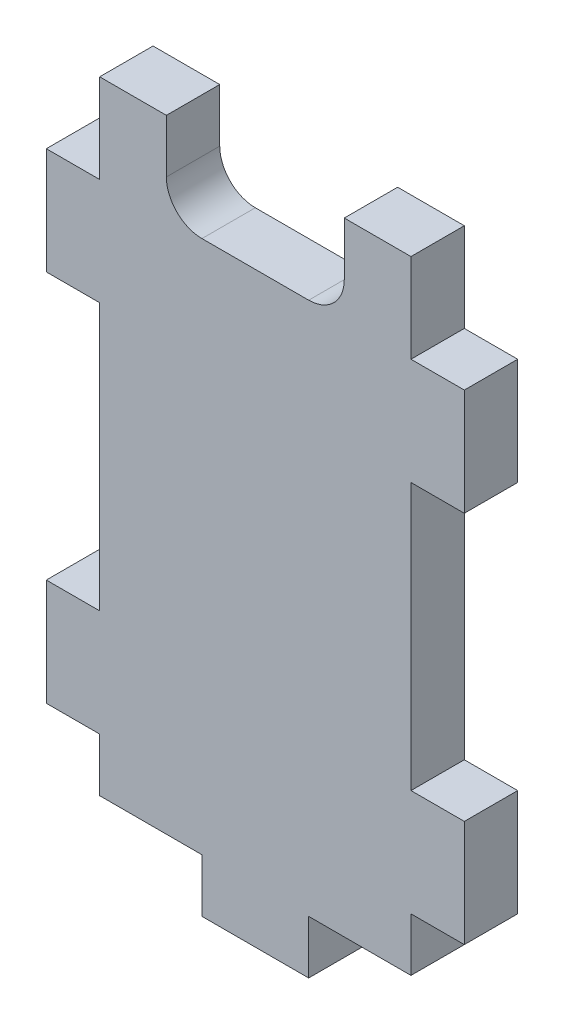
SolidWorks part; units mm, degrees
ref_plane "Front Plane" through (0, 0, 0) normal (0, 0, 1) x (1, 0, 0)
ref_plane "Top Plane" through (0, 0, 0) normal (0, 1, 0) x (1, 0, 0)
ref_plane "Right Plane" through (0, 0, 0) normal (1, 0, 0) x (0, 0, -1)
sketch "Sketch2" plane through (0, 0, 0) normal (0, 1, 0) x (1, 0, 0)
  line L0 (0, 0) -> (0, 6) construction
  dimension "D1" = 6
sketch "Sketch1" plane through (0, 0, 0) normal (0, 0, 1) x (1, 0, 0)
  line L0 (0, -35) -> (0, -41)
  line L1 (-17.5, -35) -> (17.5, -35)
  line L2 (-17.5, -35) -> (-17.5, 35)
  line L3 (-17.5, 35) -> (17.5, 35)
  line L4 (17.5, -35) -> (17.5, 35)
  line L5 (-17.5, -35) -> (17.5, 35)
  line L6 (-17.5, 35) -> (17.5, -35)
  line L7 (0, -41) -> (-6, -41)
  line L8 (-6, -41) -> (-6, -35)
  line L9 (-6, -35) -> (6, -35)
  line L10 (6, -35) -> (6, -41)
  line L11 (6, -41) -> (0, -41)
  line L12 (23.5, -29) -> (23.5, -35) construction
  line L13 (17.5, 25) -> (23.5, 25)
  line L14 (17.5, 25) -> (17.5, 13)
  line L15 (17.5, 13) -> (23.5, 13)
  line L16 (23.5, 25) -> (23.5, 13)
  line L17 (17.5, -17) -> (23.5, -17)
  line L18 (17.5, -17) -> (17.5, -29)
  line L19 (17.5, -29) -> (23.5, -29)
  line L20 (23.5, -17) -> (23.5, -29)
  line L22 (23.5, -35) -> (17.5, -35) construction
  line L23 (10, 35) -> (10, 25)
  line L24 (10, 25) -> (-10, 25)
  line L25 (-10, 25) -> (-10, 35)
  line L26 (0, 25) -> (0, 35) construction
  line L27 (17.5, 25) -> (10, 25) construction
  point P0 (0, 0)
  dimension "D1" = 70
  dimension "D2" = 35
  dimension "D3" = 6
  dimension "D4" = 12
  dimension "D5" = 12
  dimension "D6" = 10
  dimension "D7" = 20
extrude "Boss-Extrude1" add sketch "Sketch1" against normal up to vertex (6 mm away) contours L6 L2 L5 | L24 L25 L3 L6 L5 L23 | L5 L6 L4 | L6 L5 L1 | L11 L10 L1 L0 | L8 L7 L0 L1 region at (3, -38, 0) region at (-3, -38, 0) region at (0, -23.3333, 0) region at (-11.6667, 0, 0) region at (11.6667, 0, 0) region at (0, 20.101, 0) up to point (0, 0, -6)
extrude "Boss-Extrude2" add sketch "Sketch1<3>" against normal up to surface (6 mm away) contours L16 L13 L4 L15 | L20 L17 L4 L19 region at (20.5, -23, 0) region at (20.5, 19, 0) up to face at (0, -2.6667, -6)
sketch "Sketch1<3>" plane through (0, 0, 0) normal (0, 0, 1) x (1, 0, 0) same geometry as "Sketch1"
mirror "Mirror1" about plane through (0, 0, 0) normal (1, 0, 0) of "Boss-Extrude2"
fillet "Fillet2" radius 4 2 edges at (-10, 25, -3) (10, 25, -3)
equation "\"t_wood\"= 6' Thickness of the wood"
equation "\"t_glass\"= 2.5'Thickness of glass panels"
equation "\"w_glass\"= 248"
equation "\"h_glass\"= 167"
equation "\"h_food_internal\" = 60"
equation "\"entry_height\"= 20"
equation "\"entry diameter\"= 8"
equation "\"glass_bottom_overlap\"= 8"
equation "\"default_finger_size\"= 12"
equation "\"brood_depth\"= 42"
equation "\"outer_box_depth\" = \"brood_depth\" + ( 2 * \"t_glass\" ) + ( 2 * \"t_wood\" )"
equation "\"outer_box_width\"= \"w_glass\" + ( 2 * \"t_wood\" )"
equation "\"food_top_clearance\"= 10"
equation "\"outer_box_height\"= \"t_wood\" + \"h_glass\" + \"t_wood\" + \"h_food_internal\" + \"food_top_clearance\" + \"t_wood\""
equation "\"food_internal_depth\"= \"brood_depth\" + \"t_glass\" + \"t_glass\" - \"t_wood\" - \"t_wood\""
equation "\"food_channel_clearance_width\"= 14"
equation "\"bar_top_play\"= 4.5"
equation "\"bar_entry_angle\"= 10"
equation "\"bar_width\"= 20"
equation "\"entry_disk_play\"= 0.3"
equation "\"D1@Sketch2\"=\"t_wood\""
equation "\"D1@Sketch1\"=\"food_top_clearance\"+\"h_food_internal\""
equation "\"D2@Sketch1\"=\"food_internal_depth\""
equation "\"D3@Sketch1\"=\"t_wood\""
equation "\"D4@Sketch1\"=\"default_finger_size\""
equation "\"D5@Sketch1\"=\"default_finger_size\""
equation "\"D6@Sketch1\"=\"food_top_clearance\""
equation "\"D7@Sketch1\"=\"bar_width\""
